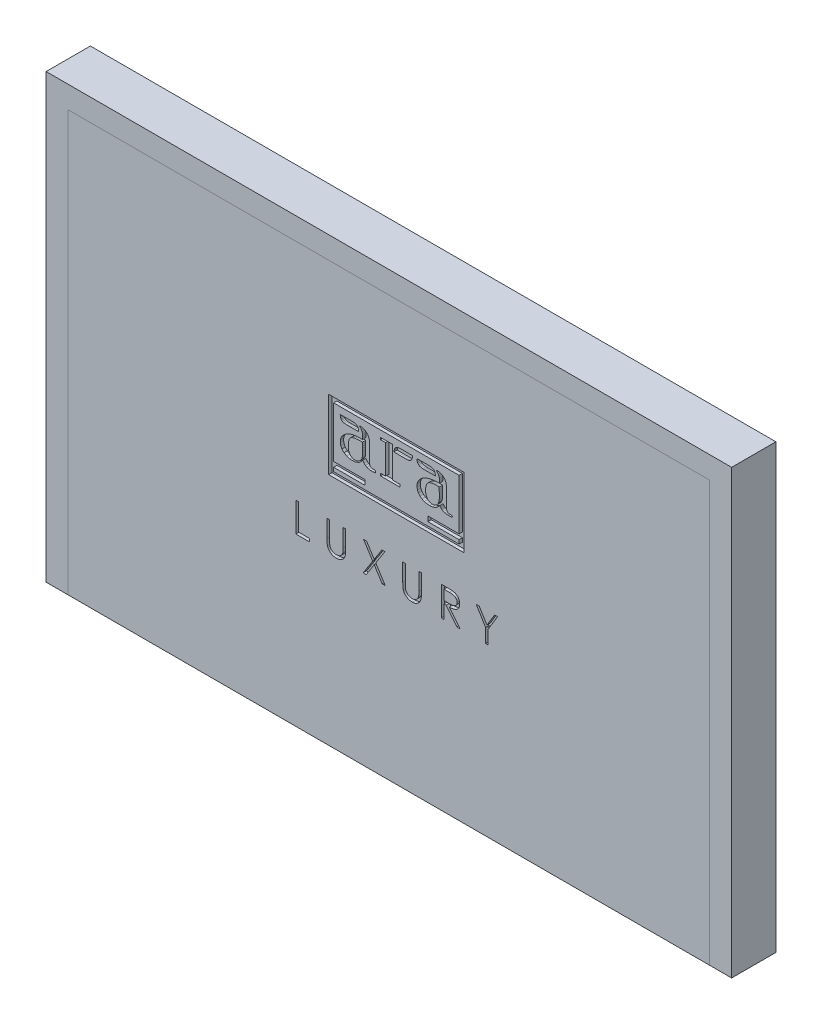
SolidWorks part; units mm, degrees
ref_plane "Front Plane" through (0, 0, 0) normal (0, 0, 1) x (1, 0, 0)
ref_plane "Top Plane" through (0, 0, 0) normal (0, 1, 0) x (1, 0, 0)
ref_plane "Right Plane" through (0, 0, 0) normal (1, 0, 0) x (0, 0, -1)
sketch "Sketch1" plane through (0, 0, 0) normal (0, 0, 1) x (1, 0, 0)
  line L0 (290, -200) -> (310, -200)
  line L1 (-310, 200) -> (310, 200)
  line L2 (-310, 200) -> (-310, -200)
  line L3 (-310, -200) -> (290, -200)
  line L4 (310, 200) -> (310, -200)
  line L5 (-310, -200) -> (-290, -200)
  line L6 (-310, -200) -> (-310, 200)
  line L7 (-310, 200) -> (-290, 200)
  line L8 (-290, -200) -> (-290, 180)
  line L9 (-310, 200) -> (310, 200)
  line L10 (-310, 200) -> (-310, 180)
  line L11 (-290, 180) -> (290, 180)
  line L12 (310, 200) -> (310, 180)
  line L13 (310, 200) -> (290, 200)
  line L14 (310, 200) -> (310, -200)
  line L15 (310, -200) -> (290, -200)
  line L16 (290, 180) -> (290, -200)
  point P0 (0, 0)
  point P7 (0, 200)
  point P8 (-310, 0)
  dimension "D1" = 620
  dimension "D2" = 400
  dimension "D3" = 20
  dimension "D4" = 20
  dimension "D5" = 20
extrude "Boss-Extrude3" add sketch "Sketch1" along normal blind 40 contours L16 L11 L8 L3 region at (0, -10, 0)
extrude "Boss-Extrude4" add sketch "Sketch1<6>" along normal blind 40 separate body contours L11 L16 L0 L4 L9 L1 L2 L6 L3 L8 region at (297.3783, -10, 0)
sketch "Sketch1<6>" plane through (0, 0, 0) normal (0, 0, 1) x (1, 0, 0) same geometry as "Sketch1"
sketch "Sketch8" plane through (0, 0, 40) normal (0, 0, 1) x (1, 0, 0)
  line L0 (-349.1542, 130) -> (342.1107, 130) construction
  line L1 (-310, 200) -> (310, 200) construction
  text T0 "LUXURY" font "Century Gothic" height in points 100
  dimension "D1" = 70
extrude "Cut-Extrude1" cut sketch "Sketch8" against normal blind 3
sketch "Sketch9" plane through (0, 0, 40) normal (0, 0, 1) x (1, 0, 0)
  line L0 (-340.0983, 130) -> (368.2721, 130) construction
  line L1 (-310, 200) -> (310, 200) construction
  dimension "D1" = 70
sketch "Sketch10" plane through (0, 0, 40) normal (0, 0, 1) x (1, 0, 0)
  line L24 (-49.9679, 20.0654) -> (-49.9679, 16.5579)
  line L25 (-21.4314, 20.0654) -> (-49.9679, 20.0654)
  line L26 (-21.4314, 24.5654) -> (-21.4314, 20.0654)
  line L27 (-49.9679, 24.5654) -> (-21.4314, 24.5654)
  line L28 (-49.9679, 70.5) -> (-49.9679, 24.5654)
  line L29 (63.4321, 70.5) -> (-49.9679, 70.5)
  line L30 (63.4321, 24.5654) -> (63.4321, 70.5)
  line L31 (35.2971, 24.5654) -> (63.4321, 24.5654)
  line L32 (35.2971, 20.0654) -> (35.2971, 24.5654)
  line L33 (63.4321, 20.0654) -> (35.2971, 20.0654)
  line L34 (63.4321, 16.5579) -> (63.4321, 20.0654)
  line L35 (-49.9679, 16.5579) -> (63.4321, 16.5579)
  line L76 (-14.5603, 25.6878) -> (-14.4285, 25.6889)
  line L77 (-14.9757, 25.6878) -> (-14.5603, 25.6878)
  line L78 (-14.9757, 27.085) -> (-14.9757, 25.6878)
  line L79 (-14.6075, 27.085) -> (-14.9757, 27.085)
  line L80 (-14.4416, 27.0821) -> (-14.6075, 27.085)
  line L81 (-14.2917, 27.0737) -> (-14.4416, 27.0821)
  line L82 (-14.1577, 27.0597) -> (-14.2917, 27.0737)
  line L83 (-14.0393, 27.0405) -> (-14.1577, 27.0597)
  line L84 (-13.9365, 27.0162) -> (-14.0393, 27.0405)
  line L85 (-13.849, 26.9869) -> (-13.9365, 27.0162)
  line L86 (-13.7767, 26.9529) -> (-13.849, 26.9869)
  line L87 (-13.6976, 26.8962) -> (-13.7767, 26.9529)
  line L88 (-13.6301, 26.8312) -> (-13.6976, 26.8962)
  line L89 (-13.5746, 26.7579) -> (-13.6301, 26.8312)
  line L90 (-13.5311, 26.676) -> (-13.5746, 26.7579)
  line L91 (-13.4998, 26.5853) -> (-13.5311, 26.676)
  line L92 (-13.481, 26.4857) -> (-13.4998, 26.5853)
  line L93 (-13.4746, 26.377) -> (-13.481, 26.4857)
  line L94 (-13.4769, 26.3134) -> (-13.4746, 26.377)
  line L95 (-13.4839, 26.2523) -> (-13.4769, 26.3134)
  line L96 (-13.4954, 26.1939) -> (-13.4839, 26.2523)
  line L97 (-13.5116, 26.1382) -> (-13.4954, 26.1939)
  line L98 (-13.5324, 26.0856) -> (-13.5116, 26.1382)
  line L99 (-13.5578, 26.0361) -> (-13.5324, 26.0856)
  line L100 (-13.5879, 25.9899) -> (-13.5578, 26.0361)
  line L101 (-13.6185, 25.9436) -> (-13.5879, 25.9899)
  line L102 (-13.6533, 25.9018) -> (-13.6185, 25.9436)
  line L103 (-13.6922, 25.8643) -> (-13.6533, 25.9018)
  line L104 (-13.7346, 25.8309) -> (-13.6922, 25.8643)
  line L105 (-13.7804, 25.8014) -> (-13.7346, 25.8309)
  line L106 (-13.8292, 25.7758) -> (-13.7804, 25.8014)
  line L107 (-13.8806, 25.7538) -> (-13.8292, 25.7758)
  line L108 (-13.943, 25.7353) -> (-13.8806, 25.7538)
  line L109 (-14.017, 25.7201) -> (-13.943, 25.7353)
  line L110 (-14.1025, 25.708) -> (-14.017, 25.7201)
  line L111 (-14.1996, 25.6989) -> (-14.1025, 25.708)
  line L112 (-14.3083, 25.6926) -> (-14.1996, 25.6989)
  line L113 (-14.4285, 25.6889) -> (-14.3083, 25.6926)
  line L184 (-36.331, 47.0631) -> (-36.431, 46.0338)
  line L185 (-36.2105, 48.0868) -> (-36.331, 47.0631)
  line L186 (-36.0553, 48.7996) -> (-36.2105, 48.0868)
  line L187 (-35.7856, 49.4505) -> (-36.0553, 48.7996)
  line L188 (-35.4123, 50.0372) -> (-35.7856, 49.4505)
  line L189 (-34.9466, 50.5572) -> (-35.4123, 50.0372)
  line L190 (-34.3994, 51.0079) -> (-34.9466, 50.5572)
  line L191 (-33.7817, 51.3869) -> (-34.3994, 51.0079)
  line L192 (-33.1046, 51.6918) -> (-33.7817, 51.3869)
  line L193 (-31.8319, 52.108) -> (-33.1046, 51.6918)
  line L194 (-30.5454, 52.4072) -> (-31.8319, 52.108)
  line L195 (-29.2481, 52.6051) -> (-30.5454, 52.4072)
  line L196 (-27.9427, 52.7178) -> (-29.2481, 52.6051)
  line L197 (-26.6321, 52.7611) -> (-27.9427, 52.7178)
  line L198 (-25.3192, 52.751) -> (-26.6321, 52.7611)
  line L199 (-24.0068, 52.7033) -> (-25.3192, 52.751)
  line L200 (-24.0016, 51.0225) -> (-24.0068, 52.7033)
  line L201 (-23.9899, 49.3656) -> (-24.0016, 51.0225)
  line L202 (-23.9775, 47.7287) -> (-23.9899, 49.3656)
  line L203 (-23.9703, 46.108) -> (-23.9775, 47.7287)
  line L204 (-23.9741, 44.4999) -> (-23.9703, 46.108)
  line L205 (-23.9947, 42.9003) -> (-23.9741, 44.4999)
  line L206 (-24.0381, 41.3057) -> (-23.9947, 42.9003)
  line L207 (-24.2689, 40.0096) -> (-24.0381, 41.3057)
  line L208 (-24.8291, 38.7828) -> (-24.2689, 40.0096)
  line L209 (-25.6608, 37.6717) -> (-24.8291, 38.7828)
  line L210 (-26.7064, 36.7225) -> (-25.6608, 37.6717)
  line L211 (-27.908, 35.9817) -> (-26.7064, 36.7225)
  line L212 (-29.2079, 35.4954) -> (-27.908, 35.9817)
  line L213 (-30.5482, 35.31) -> (-29.2079, 35.4954)
  line L214 (-31.8358, 35.4287) -> (-30.5482, 35.31)
  line L215 (-33.0328, 35.8086) -> (-31.8358, 35.4287)
  line L216 (-34.1061, 36.4284) -> (-33.0328, 35.8086)
  line L217 (-35.0224, 37.2666) -> (-34.1061, 36.4284)
  line L218 (-35.7487, 38.3016) -> (-35.0224, 37.2666)
  line L219 (-36.2518, 39.5122) -> (-35.7487, 38.3016)
  line L220 (-36.4984, 40.8767) -> (-36.2518, 39.5122)
  line L221 (-36.5546, 41.9025) -> (-36.4984, 40.8767)
  line L222 (-36.5724, 42.9332) -> (-36.5546, 41.9025)
  line L223 (-36.5553, 43.9667) -> (-36.5724, 42.9332)
  line L224 (-36.507, 45.0009) -> (-36.5553, 43.9667)
  line L225 (-36.431, 46.0338) -> (-36.507, 45.0009)
  line L268 (35.6902, 50.7229) -> (35.3135, 50.4294)
  line L269 (36.092, 50.9831) -> (35.6902, 50.7229)
  line L270 (36.5053, 51.2052) -> (36.092, 50.9831)
  line L271 (36.9164, 51.3843) -> (36.5053, 51.2052)
  line L272 (38.1178, 51.7846) -> (36.9164, 51.3843)
  line L273 (39.3336, 52.0756) -> (38.1178, 51.7846)
  line L274 (40.5593, 52.2699) -> (39.3336, 52.0756)
  line L275 (41.79, 52.3798) -> (40.5593, 52.2699)
  line L276 (43.021, 52.4178) -> (41.79, 52.3798)
  line L277 (44.2478, 52.3964) -> (43.021, 52.4178)
  line L278 (45.4654, 52.328) -> (44.2478, 52.3964)
  line L279 (45.4886, 50.7056) -> (45.4654, 52.328)
  line L280 (45.5412, 49.0885) -> (45.4886, 50.7056)
  line L281 (45.5977, 47.479) -> (45.5412, 49.0885)
  line L282 (45.6329, 45.8793) -> (45.5977, 47.479)
  line L283 (45.6213, 44.2918) -> (45.6329, 45.8793)
  line L284 (45.5376, 42.7186) -> (45.6213, 44.2918)
  line L285 (45.3564, 41.1622) -> (45.5376, 42.7186)
  line L286 (44.7591, 39.2392) -> (45.3564, 41.1622)
  line L287 (43.6933, 37.6897) -> (44.7591, 39.2392)
  line L288 (42.2799, 36.554) -> (43.6933, 37.6897)
  line L289 (40.6393, 35.8726) -> (42.2799, 36.554)
  line L290 (38.8922, 35.6856) -> (40.6393, 35.8726)
  line L291 (37.1593, 36.0334) -> (38.8922, 35.6856)
  line L292 (35.5611, 36.9565) -> (37.1593, 36.0334)
  line L293 (35.3751, 37.1123) -> (35.5611, 36.9565)
  line L294 (35.1901, 37.2758) -> (35.3751, 37.1123)
  line L295 (35.0106, 37.4472) -> (35.1901, 37.2758)
  line L296 (34.8411, 37.6268) -> (35.0106, 37.4472)
  line L297 (34.6863, 37.8148) -> (34.8411, 37.6268)
  line L298 (34.5506, 38.0113) -> (34.6863, 37.8148)
  line L299 (34.4384, 38.2167) -> (34.5506, 38.0113)
  line L300 (33.794, 39.8153) -> (34.4384, 38.2167)
  line L301 (33.3635, 41.4187) -> (33.794, 39.8153)
  line L302 (33.1485, 43.024) -> (33.3635, 41.4187)
  line L303 (33.1503, 44.6277) -> (33.1485, 43.024)
  line L304 (33.3703, 46.2269) -> (33.1503, 44.6277)
  line L305 (33.8099, 47.8183) -> (33.3703, 46.2269)
  line L306 (34.4705, 49.3987) -> (33.8099, 47.8183)
  line L307 (34.69, 49.7624) -> (34.4705, 49.3987)
  line L308 (34.9756, 50.1076) -> (34.69, 49.7624)
  line L309 (35.3135, 50.4294) -> (34.9756, 50.1076)
  line L344 (-1.446, 25.6878) -> (-1.2755, 25.6912)
  line L345 (-1.8519, 25.6878) -> (-1.446, 25.6878)
  line L346 (-1.8519, 27.085) -> (-1.8519, 25.6878)
  line L347 (-1.4932, 27.085) -> (-1.8519, 27.085)
  line L348 (-1.3504, 27.0833) -> (-1.4932, 27.085)
  line L349 (-1.2213, 27.0783) -> (-1.3504, 27.0833)
  line L350 (-1.1058, 27.0701) -> (-1.2213, 27.0783)
  line L351 (-1.0036, 27.059) -> (-1.1058, 27.0701)
  line L352 (-0.9146, 27.0451) -> (-1.0036, 27.059)
  line L353 (-0.8387, 27.0285) -> (-0.9146, 27.0451)
  line L354 (-0.7757, 27.0095) -> (-0.8387, 27.0285)
  line L355 (-0.7242, 26.9875) -> (-0.7757, 27.0095)
  line L356 (-0.6751, 26.9619) -> (-0.7242, 26.9875)
  line L357 (-0.6283, 26.9325) -> (-0.6751, 26.9619)
  line L358 (-0.5837, 26.8991) -> (-0.6283, 26.9325)
  line L359 (-0.5416, 26.8616) -> (-0.5837, 26.8991)
  line L360 (-0.5017, 26.8198) -> (-0.5416, 26.8616)
  line L361 (-0.4641, 26.7735) -> (-0.5017, 26.8198)
  line L362 (-0.434, 26.7273) -> (-0.4641, 26.7735)
  line L363 (-0.4086, 26.6778) -> (-0.434, 26.7273)
  line L364 (-0.3878, 26.6251) -> (-0.4086, 26.6778)
  line L365 (-0.3716, 26.5695) -> (-0.3878, 26.6251)
  line L366 (-0.36, 26.511) -> (-0.3716, 26.5695)
  line L367 (-0.3531, 26.45) -> (-0.36, 26.511)
  line L368 (-0.3508, 26.3864) -> (-0.3531, 26.45)
  line L369 (-0.3554, 26.2852) -> (-0.3508, 26.3864)
  line L370 (-0.3695, 26.1922) -> (-0.3554, 26.2852)
  line L371 (-0.3932, 26.1072) -> (-0.3695, 26.1922)
  line L372 (-0.4266, 26.0303) -> (-0.3932, 26.1072)
  line L373 (-0.4699, 25.9615) -> (-0.4266, 26.0303)
  line L374 (-0.5232, 25.9008) -> (-0.4699, 25.9615)
  line L375 (-0.5869, 25.8482) -> (-0.5232, 25.9008)
  line L376 (-0.6602, 25.8066) -> (-0.5869, 25.8482)
  line L377 (-0.7506, 25.771) -> (-0.6602, 25.8066)
  line L378 (-0.8576, 25.7415) -> (-0.7506, 25.771)
  line L379 (-0.981, 25.7182) -> (-0.8576, 25.7415)
  line L380 (-1.1204, 25.7014) -> (-0.981, 25.7182)
  line L381 (-1.2755, 25.6912) -> (-1.1204, 25.7014)
  line L851 (28.2851, 24.6115) -> (30.702, 24.6115)
  line L852 (30.702, 24.6115) -> (30.702, 25.8577)
  line L853 (30.702, 25.8577) -> (28.2851, 25.8577)
  line L854 (28.2851, 25.8577) -> (28.2851, 27.0756)
  line L855 (28.2851, 27.0756) -> (30.702, 27.0756)
  line L856 (30.702, 27.0756) -> (30.702, 28.3407)
  line L857 (30.702, 28.3407) -> (27.0011, 28.3407)
  line L858 (27.0011, 28.3407) -> (27.0011, 21.562)
  line L859 (27.0011, 21.562) -> (30.702, 21.562)
  line L860 (30.702, 21.562) -> (30.702, 22.827)
  line L861 (30.702, 22.827) -> (28.2851, 22.827)
  line L862 (28.2851, 22.827) -> (28.2851, 24.6115)
  line L863 (24.5286, 21.562) -> (23.3957, 28.3407)
  line L864 (23.3957, 28.3407) -> (22.14, 28.3407)
  line L865 (22.14, 28.3407) -> (20.5633, 23.6107)
  line L866 (20.5633, 23.6107) -> (18.9772, 28.3407)
  line L867 (18.9772, 28.3407) -> (17.731, 28.3407)
  line L868 (17.731, 28.3407) -> (16.5603, 21.562)
  line L869 (16.5603, 21.562) -> (17.8159, 21.562)
  line L870 (17.8159, 21.562) -> (18.5618, 25.8388)
  line L871 (18.5618, 25.8388) -> (19.9874, 21.562)
  line L872 (19.9874, 21.562) -> (21.1204, 21.562)
  line L873 (21.1204, 21.562) -> (22.5648, 25.8388)
  line L874 (22.5648, 25.8388) -> (23.2824, 21.562)
  line L875 (23.2824, 21.562) -> (24.5286, 21.562)
  line L876 (10.8683, 23.8046) -> (10.866, 23.9601)
  line L877 (10.866, 23.9601) -> (10.866, 28.3407)
  line L878 (10.866, 28.3407) -> (9.5725, 28.3407)
  line L879 (9.5725, 28.3407) -> (9.5725, 24.3)
  line L880 (9.5725, 24.3) -> (9.5772, 23.967)
  line L881 (9.5772, 23.967) -> (9.5913, 23.6637)
  line L882 (9.5913, 23.6637) -> (9.6149, 23.3898)
  line L883 (9.6149, 23.3898) -> (9.6483, 23.145)
  line L884 (9.6483, 23.145) -> (9.6916, 22.9289)
  line L885 (9.6916, 22.9289) -> (9.7449, 22.7412)
  line L886 (9.7449, 22.7412) -> (9.8085, 22.5816)
  line L887 (9.8085, 22.5816) -> (9.8802, 22.4394)
  line L888 (9.8802, 22.4394) -> (9.9656, 22.3042)
  line L889 (9.9656, 22.3042) -> (10.0645, 22.1758)
  line L890 (10.0645, 22.1758) -> (10.1767, 22.0545)
  line L891 (10.1767, 22.0545) -> (10.3022, 21.94)
  line L892 (10.3022, 21.94) -> (10.4408, 21.8325)
  line L893 (10.4408, 21.8325) -> (10.5922, 21.7319)
  line L894 (10.5922, 21.7319) -> (10.75, 21.6418)
  line L895 (10.75, 21.6418) -> (10.9159, 21.5655)
  line L896 (10.9159, 21.5655) -> (11.0899, 21.503)
  line L897 (11.0899, 21.503) -> (11.2719, 21.4545)
  line L898 (11.2719, 21.4545) -> (11.4621, 21.4198)
  line L899 (11.4621, 21.4198) -> (11.6604, 21.399)
  line L900 (11.6604, 21.399) -> (11.8667, 21.392)
  line L901 (11.8667, 21.392) -> (12.0257, 21.3955)
  line L902 (12.0257, 21.3955) -> (12.1789, 21.4061)
  line L903 (12.1789, 21.4061) -> (12.3263, 21.424)
  line L904 (12.3263, 21.424) -> (12.4679, 21.4493)
  line L905 (12.4679, 21.4493) -> (12.6037, 21.4822)
  line L906 (12.6037, 21.4822) -> (12.7338, 21.5228)
  line L907 (12.7338, 21.5228) -> (12.858, 21.5714)
  line L908 (12.858, 21.5714) -> (12.9771, 21.6245)
  line L909 (12.9771, 21.6245) -> (13.0918, 21.6866)
  line L910 (13.0918, 21.6866) -> (13.2021, 21.7572)
  line L911 (13.2021, 21.7572) -> (13.3083, 21.8361)
  line L912 (13.3083, 21.8361) -> (13.4106, 21.9229)
  line L913 (13.4106, 21.9229) -> (13.509, 22.0173)
  line L914 (13.509, 22.0173) -> (13.6038, 22.119)
  line L915 (13.6038, 22.119) -> (13.6928, 22.2248)
  line L916 (13.6928, 22.2248) -> (13.7736, 22.3317)
  line L917 (13.7736, 22.3317) -> (13.8459, 22.4398)
  line L918 (13.8459, 22.4398) -> (13.9096, 22.5491)
  line L919 (13.9096, 22.5491) -> (13.9646, 22.6595)
  line L920 (13.9646, 22.6595) -> (14.0107, 22.771)
  line L921 (14.0107, 22.771) -> (14.0476, 22.8838)
  line L922 (14.0476, 22.8838) -> (14.0777, 23.0098)
  line L923 (14.0777, 23.0098) -> (14.1031, 23.1612)
  line L924 (14.1031, 23.1612) -> (14.1239, 23.3381)
  line L925 (14.1239, 23.3381) -> (14.1401, 23.5404)
  line L926 (14.1401, 23.5404) -> (14.1516, 23.7682)
  line L927 (14.1516, 23.7682) -> (14.1586, 24.0213)
  line L928 (14.1586, 24.0213) -> (14.1609, 24.3)
  line L929 (14.1609, 24.3) -> (14.1609, 28.3407)
  line L930 (14.1609, 28.3407) -> (12.8674, 28.3407)
  line L931 (12.8674, 28.3407) -> (12.8674, 24.1205)
  line L932 (12.8674, 24.1205) -> (12.8657, 23.932)
  line L933 (12.8657, 23.932) -> (12.8603, 23.7629)
  line L934 (12.8603, 23.7629) -> (12.8511, 23.6127)
  line L935 (12.8511, 23.6127) -> (12.838, 23.4812)
  line L936 (12.838, 23.4812) -> (12.8207, 23.368)
  line L937 (12.8207, 23.368) -> (12.7991, 23.2728)
  line L938 (12.7991, 23.2728) -> (12.773, 23.1953)
  line L939 (12.773, 23.1953) -> (12.7418, 23.1283)
  line L940 (12.7418, 23.1283) -> (12.7049, 23.0647)
  line L941 (12.7049, 23.0647) -> (12.6621, 23.0045)
  line L942 (12.6621, 23.0045) -> (12.6135, 22.9479)
  line L943 (12.6135, 22.9479) -> (12.5592, 22.8947)
  line L944 (12.5592, 22.8947) -> (12.4991, 22.845)
  line L945 (12.4991, 22.845) -> (12.4332, 22.7988)
  line L946 (12.4332, 22.7988) -> (12.3591, 22.7572)
  line L947 (12.3591, 22.7572) -> (12.2824, 22.7215)
  line L948 (12.2824, 22.7215) -> (12.2028, 22.692)
  line L949 (12.2028, 22.692) -> (12.1198, 22.6687)
  line L950 (12.1198, 22.6687) -> (12.0333, 22.6519)
  line L951 (12.0333, 22.6519) -> (11.9427, 22.6417)
  line L952 (11.9427, 22.6417) -> (11.8479, 22.6383)
  line L953 (11.8479, 22.6383) -> (11.7566, 22.6411)
  line L954 (11.7566, 22.6411) -> (11.6689, 22.6498)
  line L955 (11.6689, 22.6498) -> (11.585, 22.6643)
  line L956 (11.585, 22.6643) -> (11.5051, 22.6845)
  line L957 (11.5051, 22.6845) -> (11.4293, 22.7105)
  line L958 (11.4293, 22.7105) -> (11.3578, 22.7423)
  line L959 (11.3578, 22.7423) -> (11.2908, 22.7798)
  line L960 (11.2908, 22.7798) -> (11.2289, 22.8221)
  line L961 (11.2289, 22.8221) -> (11.1727, 22.8679)
  line L962 (11.1727, 22.8679) -> (11.1219, 22.9176)
  line L963 (11.1219, 22.9176) -> (11.0763, 22.9712)
  line L964 (11.0763, 22.9712) -> (11.0359, 23.029)
  line L965 (11.0359, 23.029) -> (11.0005, 23.091)
  line L966 (11.0005, 23.091) -> (10.9698, 23.1575)
  line L967 (10.9698, 23.1575) -> (10.9432, 23.2297)
  line L968 (10.9432, 23.2297) -> (10.9203, 23.3166)
  line L969 (10.9203, 23.3166) -> (10.9012, 23.4179)
  line L970 (10.9012, 23.4179) -> (10.886, 23.5332)
  line L971 (10.886, 23.5332) -> (10.875, 23.6622)
  line L972 (10.875, 23.6622) -> (10.8683, 23.8046)
  line L973 (4.9749, 27.0944) -> (7.0519, 27.0944)
  line L974 (7.0519, 27.0944) -> (7.0519, 28.3407)
  line L975 (7.0519, 28.3407) -> (3.6908, 28.3407)
  line L976 (3.6908, 28.3407) -> (3.6908, 21.562)
  line L977 (3.6908, 21.562) -> (4.9749, 21.562)
  line L978 (4.9749, 21.562) -> (4.9749, 24.6115)
  line L979 (4.9749, 24.6115) -> (7.0519, 24.6115)
  line L980 (7.0519, 24.6115) -> (7.0519, 25.8577)
  line L981 (7.0519, 25.8577) -> (4.9749, 25.8577)
  line L982 (4.9749, 25.8577) -> (4.9749, 27.0944)
  line L983 (-1.7198, 24.4321) -> (-0.1998, 21.562)
  line L984 (-0.1998, 21.562) -> (1.2164, 21.562)
  line L985 (1.2164, 21.562) -> (-0.3886, 24.5737)
  line L986 (-0.3886, 24.5737) -> (-0.2094, 24.6431)
  line L987 (-0.2094, 24.6431) -> (-0.0441, 24.7217)
  line L988 (-0.0441, 24.7217) -> (0.1074, 24.8095)
  line L989 (0.1074, 24.8095) -> (0.2449, 24.9066)
  line L990 (0.2449, 24.9066) -> (0.3686, 25.013)
  line L991 (0.3686, 25.013) -> (0.4784, 25.1286)
  line L992 (0.4784, 25.1286) -> (0.5744, 25.2535)
  line L993 (0.5744, 25.2535) -> (0.6606, 25.3871)
  line L994 (0.6606, 25.3871) -> (0.733, 25.5291)
  line L995 (0.733, 25.5291) -> (0.7919, 25.6798)
  line L996 (0.7919, 25.6798) -> (0.8374, 25.8396)
  line L997 (0.8374, 25.8396) -> (0.8697, 26.0089)
  line L998 (0.8697, 26.0089) -> (0.889, 26.1879)
  line L999 (0.889, 26.1879) -> (0.8954, 26.377)
  line L1000 (0.8954, 26.377) -> (0.8896, 26.5521)
  line L1001 (0.8896, 26.5521) -> (0.872, 26.7212)
  line L1002 (0.872, 26.7212) -> (0.8426, 26.8843)
  line L1003 (0.8426, 26.8843) -> (0.8011, 27.0411)
  line L1004 (0.8011, 27.0411) -> (0.7474, 27.1914)
  line L1005 (0.7474, 27.1914) -> (0.6814, 27.3352)
  line L1006 (0.6814, 27.3352) -> (0.6028, 27.4721)
  line L1007 (0.6028, 27.4721) -> (0.5178, 27.6004)
  line L1008 (0.5178, 27.6004) -> (0.4247, 27.7181)
  line L1009 (0.4247, 27.7181) -> (0.3235, 27.8251)
  line L1010 (0.3235, 27.8251) -> (0.2143, 27.9212)
  line L1011 (0.2143, 27.9212) -> (0.0969, 28.0063)
  line L1012 (0.0969, 28.0063) -> (-0.0285, 28.0801)
  line L1013 (-0.0285, 28.0801) -> (-0.162, 28.1425)
  line L1014 (-0.162, 28.1425) -> (-0.3124, 28.1951)
  line L1015 (-0.3124, 28.1951) -> (-0.4885, 28.2396)
  line L1016 (-0.4885, 28.2396) -> (-0.6907, 28.276)
  line L1017 (-0.6907, 28.276) -> (-0.9193, 28.3043)
  line L1018 (-0.9193, 28.3043) -> (-1.1747, 28.3245)
  line L1019 (-1.1747, 28.3245) -> (-1.4571, 28.3366)
  line L1020 (-1.4571, 28.3366) -> (-1.767, 28.3407)
  line L1021 (-1.767, 28.3407) -> (-3.136, 28.3407)
  line L1022 (-3.136, 28.3407) -> (-3.136, 21.562)
  line L1023 (-3.136, 21.562) -> (-1.8519, 21.562)
  line L1024 (-1.8519, 21.562) -> (-1.8519, 24.4321)
  line L1025 (-1.8519, 24.4321) -> (-1.7198, 24.4321)
  line L1026 (-9.5371, 21.562) -> (-5.8361, 21.562)
  line L1027 (-5.8361, 21.562) -> (-5.8361, 22.827)
  line L1028 (-5.8361, 22.827) -> (-8.2531, 22.827)
  line L1029 (-8.2531, 22.827) -> (-8.2531, 24.6115)
  line L1030 (-8.2531, 24.6115) -> (-5.8361, 24.6115)
  line L1031 (-5.8361, 24.6115) -> (-5.8361, 25.8577)
  line L1032 (-5.8361, 25.8577) -> (-8.2531, 25.8577)
  line L1033 (-8.2531, 25.8577) -> (-8.2531, 27.0756)
  line L1034 (-8.2531, 27.0756) -> (-5.8361, 27.0756)
  line L1035 (-5.8361, 27.0756) -> (-5.8361, 28.3407)
  line L1036 (-5.8361, 28.3407) -> (-9.5371, 28.3407)
  line L1037 (-9.5371, 28.3407) -> (-9.5371, 21.562)
  line L1038 (-14.5843, 28.3366) -> (-14.8907, 28.3407)
  line L1039 (-14.8907, 28.3407) -> (-16.2597, 28.3407)
  line L1040 (-16.2597, 28.3407) -> (-16.2597, 21.562)
  line L1041 (-16.2597, 21.562) -> (-14.9757, 21.562)
  line L1042 (-14.9757, 21.562) -> (-14.9757, 24.4321)
  line L1043 (-14.9757, 24.4321) -> (-14.7052, 24.4344)
  line L1044 (-14.7052, 24.4344) -> (-14.4599, 24.4411)
  line L1045 (-14.4599, 24.4411) -> (-14.2397, 24.4522)
  line L1046 (-14.2397, 24.4522) -> (-14.0445, 24.4673)
  line L1047 (-14.0445, 24.4673) -> (-13.8741, 24.4864)
  line L1048 (-13.8741, 24.4864) -> (-13.7282, 24.5094)
  line L1049 (-13.7282, 24.5094) -> (-13.6068, 24.5359)
  line L1050 (-13.6068, 24.5359) -> (-13.4304, 24.5943)
  line L1051 (-13.4304, 24.5943) -> (-13.2653, 24.6645)
  line L1052 (-13.2653, 24.6645) -> (-13.1111, 24.7465)
  line L1053 (-13.1111, 24.7465) -> (-12.9674, 24.8406)
  line L1054 (-12.9674, 24.8406) -> (-12.834, 24.9469)
  line L1055 (-12.834, 24.9469) -> (-12.7105, 25.0656)
  line L1056 (-12.7105, 25.0656) -> (-12.5965, 25.1968)
  line L1057 (-12.5965, 25.1968) -> (-12.4989, 25.335)
  line L1058 (-12.4989, 25.335) -> (-12.4162, 25.4828)
  line L1059 (-12.4162, 25.4828) -> (-12.3486, 25.6405)
  line L1060 (-12.3486, 25.6405) -> (-12.296, 25.8085)
  line L1061 (-12.296, 25.8085) -> (-12.2584, 25.987)
  line L1062 (-12.2584, 25.987) -> (-12.2359, 26.1763)
  line L1063 (-12.2359, 26.1763) -> (-12.2284, 26.377)
  line L1064 (-12.2284, 26.377) -> (-12.2342, 26.5556)
  line L1065 (-12.2342, 26.5556) -> (-12.2515, 26.727)
  line L1066 (-12.2515, 26.727) -> (-12.2804, 26.8912)
  line L1067 (-12.2804, 26.8912) -> (-12.3209, 27.048)
  line L1068 (-12.3209, 27.048) -> (-12.3729, 27.1972)
  line L1069 (-12.3729, 27.1972) -> (-12.4364, 27.3386)
  line L1070 (-12.4364, 27.3386) -> (-12.5116, 27.4721)
  line L1071 (-12.5116, 27.4721) -> (-12.5966, 27.5969)
  line L1072 (-12.5966, 27.5969) -> (-12.6899, 27.7121)
  line L1073 (-12.6899, 27.7121) -> (-12.7915, 27.8174)
  line L1074 (-12.7915, 27.8174) -> (-12.9018, 27.9125)
  line L1075 (-12.9018, 27.9125) -> (-13.0208, 27.997)
  line L1076 (-13.0208, 27.997) -> (-13.1487, 28.0706)
  line L1077 (-13.1487, 28.0706) -> (-13.2857, 28.133)
  line L1078 (-13.2857, 28.133) -> (-13.4396, 28.1891)
  line L1079 (-13.4396, 28.1891) -> (-13.618, 28.2361)
  line L1080 (-13.618, 28.2361) -> (-13.8213, 28.2742)
  line L1081 (-13.8213, 28.2742) -> (-14.05, 28.3035)
  line L1082 (-14.05, 28.3035) -> (-14.3042, 28.3243)
  line L1083 (-14.3042, 28.3243) -> (-14.5843, 28.3366)
  line L1084 (30.0246, 35.1575) -> (32.0574, 34.2463)
  line L1085 (32.0574, 34.2463) -> (34.3493, 33.63)
  line L1086 (34.3493, 33.63) -> (36.7974, 33.3967)
  line L1087 (36.7974, 33.3967) -> (39.2986, 33.6344)
  line L1088 (39.2986, 33.6344) -> (41.7497, 34.4312)
  line L1089 (41.7497, 34.4312) -> (44.0476, 35.8751)
  line L1090 (44.0476, 35.8751) -> (46.0892, 38.054)
  line L1091 (46.0892, 38.054) -> (46.4015, 37.6887)
  line L1092 (46.4015, 37.6887) -> (46.6989, 37.3226)
  line L1093 (46.6989, 37.3226) -> (46.9887, 36.9622)
  line L1094 (46.9887, 36.9622) -> (47.278, 36.6141)
  line L1095 (47.278, 36.6141) -> (47.5741, 36.2848)
  line L1096 (47.5741, 36.2848) -> (47.8842, 35.981)
  line L1097 (47.8842, 35.981) -> (48.2156, 35.7093)
  line L1098 (48.2156, 35.7093) -> (49.3955, 35.0153)
  line L1099 (49.3955, 35.0153) -> (50.6215, 34.5922)
  line L1100 (50.6215, 34.5922) -> (51.883, 34.3794)
  line L1101 (51.883, 34.3794) -> (53.1694, 34.3163)
  line L1102 (53.1694, 34.3163) -> (54.47, 34.3422)
  line L1103 (54.47, 34.3422) -> (55.7744, 34.3965)
  line L1104 (55.7744, 34.3965) -> (57.0718, 34.4186)
  line L1105 (57.0718, 34.4186) -> (57.1431, 34.4445)
  line L1106 (57.1431, 34.4445) -> (57.2248, 34.515)
  line L1107 (57.2248, 34.515) -> (57.3083, 34.6171)
  line L1108 (57.3083, 34.6171) -> (57.3847, 34.7377)
  line L1109 (57.3847, 34.7377) -> (57.4453, 34.8638)
  line L1110 (57.4453, 34.8638) -> (57.4813, 34.9824)
  line L1111 (57.4813, 34.9824) -> (57.484, 35.0805)
  line L1112 (57.484, 35.0805) -> (57.4482, 35.1997)
  line L1113 (57.4482, 35.1997) -> (57.39, 35.3222)
  line L1114 (57.39, 35.3222) -> (57.3135, 35.4422)
  line L1115 (57.3135, 35.4422) -> (57.2229, 35.5535)
  line L1116 (57.2229, 35.5535) -> (57.1221, 35.6504)
  line L1117 (57.1221, 35.6504) -> (57.0153, 35.7269)
  line L1118 (57.0153, 35.7269) -> (56.9066, 35.777)
  line L1119 (56.9066, 35.777) -> (56.7416, 35.8177)
  line L1120 (56.7416, 35.8177) -> (56.5703, 35.8387)
  line L1121 (56.5703, 35.8387) -> (56.3943, 35.8451)
  line L1122 (56.3943, 35.8451) -> (56.2152, 35.8418)
  line L1123 (56.2152, 35.8418) -> (56.0346, 35.8337)
  line L1124 (56.0346, 35.8337) -> (55.8541, 35.8259)
  line L1125 (55.8541, 35.8259) -> (55.6755, 35.8232)
  line L1126 (55.6755, 35.8232) -> (54.6038, 35.8849)
  line L1127 (54.6038, 35.8849) -> (53.7564, 36.0637)
  line L1128 (53.7564, 36.0637) -> (53.1115, 36.3808)
  line L1129 (53.1115, 36.3808) -> (52.6473, 36.8577)
  line L1130 (52.6473, 36.8577) -> (52.342, 37.5157)
  line L1131 (52.342, 37.5157) -> (52.1736, 38.3763)
  line L1132 (52.1736, 38.3763) -> (52.1205, 39.4608)
  line L1133 (52.1205, 39.4608) -> (52.1187, 41.8984)
  line L1134 (52.1187, 41.8984) -> (52.1209, 44.3361)
  line L1135 (52.1209, 44.3361) -> (52.1223, 46.7738)
  line L1136 (52.1223, 46.7738) -> (52.1179, 49.2114)
  line L1137 (52.1179, 49.2114) -> (52.1028, 51.6488)
  line L1138 (52.1028, 51.6488) -> (52.0719, 54.0858)
  line L1139 (52.0719, 54.0858) -> (52.0202, 56.5222)
  line L1140 (52.0202, 56.5222) -> (51.7376, 58.485)
  line L1141 (51.7376, 58.485) -> (51.0288, 60.2277)
  line L1142 (51.0288, 60.2277) -> (49.9404, 61.712)
  line L1143 (49.9404, 61.712) -> (48.5193, 62.8992)
  line L1144 (48.5193, 62.8992) -> (46.812, 63.7509)
  line L1145 (46.812, 63.7509) -> (44.8655, 64.2285)
  line L1146 (44.8655, 64.2285) -> (42.7263, 64.2935)
  line L1147 (42.7263, 64.2935) -> (43.8833, 63.2375)
  line L1148 (43.8833, 63.2375) -> (44.7298, 62.0929)
  line L1149 (44.7298, 62.0929) -> (45.3047, 60.8675)
  line L1150 (45.3047, 60.8675) -> (45.647, 59.5694)
  line L1151 (45.647, 59.5694) -> (45.7956, 58.2066)
  line L1152 (45.7956, 58.2066) -> (45.7895, 56.7872)
  line L1153 (45.7895, 56.7872) -> (45.6677, 55.3191)
  line L1154 (45.6677, 55.3191) -> (44.9658, 55.2888)
  line L1155 (44.9658, 55.2888) -> (44.2691, 55.2626)
  line L1156 (44.2691, 55.2626) -> (43.577, 55.2373)
  line L1157 (43.577, 55.2373) -> (42.8889, 55.2097)
  line L1158 (42.8889, 55.2097) -> (42.2041, 55.1763)
  line L1159 (42.2041, 55.1763) -> (41.522, 55.134)
  line L1160 (41.522, 55.134) -> (40.842, 55.0793)
  line L1161 (40.842, 55.0793) -> (38.5523, 54.7986)
  line L1162 (38.5523, 54.7986) -> (36.34, 54.3553)
  line L1163 (36.34, 54.3553) -> (34.2232, 53.7125)
  line L1164 (34.2232, 53.7125) -> (32.2204, 52.8331)
  line L1165 (32.2204, 52.8331) -> (30.3497, 51.6802)
  line L1166 (30.3497, 51.6802) -> (28.6296, 50.2169)
  line L1167 (28.6296, 50.2169) -> (27.0782, 48.4062)
  line L1168 (27.0782, 48.4062) -> (25.9853, 46.4329)
  line L1169 (25.9853, 46.4329) -> (25.4336, 44.3248)
  line L1170 (25.4336, 44.3248) -> (25.4012, 42.1791)
  line L1171 (25.4012, 42.1791) -> (25.866, 40.0925)
  line L1172 (25.866, 40.0925) -> (26.8062, 38.1621)
  line L1173 (26.8062, 38.1621) -> (28.1997, 36.4848)
  line L1174 (28.1997, 36.4848) -> (30.0246, 35.1575)
  line L1175 (40.6634, 63.3372) -> (39.9178, 63.9071)
  line L1176 (39.9178, 63.9071) -> (39.0174, 64.2756)
  line L1177 (39.0174, 64.2756) -> (37.9599, 64.4357)
  line L1178 (37.9599, 64.4357) -> (36.1732, 64.5001)
  line L1179 (36.1732, 64.5001) -> (34.3834, 64.5314)
  line L1180 (34.3834, 64.5314) -> (32.5894, 64.5381)
  line L1181 (32.5894, 64.5381) -> (30.7901, 64.5286)
  line L1182 (30.7901, 64.5286) -> (28.9844, 64.5114)
  line L1183 (28.9844, 64.5114) -> (27.171, 64.4949)
  line L1184 (27.171, 64.4949) -> (25.3489, 64.4875)
  line L1185 (25.3489, 64.4875) -> (25.4539, 63.1702)
  line L1186 (25.4539, 63.1702) -> (25.7705, 62.0346)
  line L1187 (25.7705, 62.0346) -> (26.2959, 61.0851)
  line L1188 (26.2959, 61.0851) -> (27.0272, 60.326)
  line L1189 (27.0272, 60.326) -> (27.9613, 59.7617)
  line L1190 (27.9613, 59.7617) -> (29.0954, 59.3965)
  line L1191 (29.0954, 59.3965) -> (30.4266, 59.2347)
  line L1192 (30.4266, 59.2347) -> (31.4662, 59.2013)
  line L1193 (31.4662, 59.2013) -> (32.5065, 59.1836)
  line L1194 (32.5065, 59.1836) -> (33.5472, 59.1775)
  line L1195 (33.5472, 59.1775) -> (34.5882, 59.1792)
  line L1196 (34.5882, 59.1792) -> (35.6294, 59.1845)
  line L1197 (35.6294, 59.1845) -> (36.6705, 59.1895)
  line L1198 (36.6705, 59.1895) -> (37.7114, 59.1903)
  line L1199 (37.7114, 59.1903) -> (38.3437, 59.1889)
  line L1200 (38.3437, 59.1889) -> (38.9762, 59.1884)
  line L1201 (38.9762, 59.1884) -> (39.6089, 59.1883)
  line L1202 (39.6089, 59.1883) -> (40.2419, 59.1886)
  line L1203 (40.2419, 59.1886) -> (40.8752, 59.1891)
  line L1204 (40.8752, 59.1891) -> (41.5091, 59.1895)
  line L1205 (41.5091, 59.1895) -> (42.1435, 59.1897)
  line L1206 (42.1435, 59.1897) -> (41.9942, 60.4923)
  line L1207 (41.9942, 60.4923) -> (41.6992, 61.6226)
  line L1208 (41.6992, 61.6226) -> (41.2564, 62.5733)
  line L1209 (41.2564, 62.5733) -> (40.6634, 63.3372)
  line L1210 (9.8323, 64.8007) -> (8.4739, 64.6629)
  line L1211 (8.4739, 64.6629) -> (7.3263, 64.3141)
  line L1212 (7.3263, 64.3141) -> (6.384, 63.7507)
  line L1213 (6.384, 63.7507) -> (5.6417, 62.9689)
  line L1214 (5.6417, 62.9689) -> (5.094, 61.9649)
  line L1215 (5.094, 61.9649) -> (4.7357, 60.7352)
  line L1216 (4.7357, 60.7352) -> (4.5614, 59.276)
  line L1217 (4.5614, 59.276) -> (6.3614, 59.2678)
  line L1218 (6.3614, 59.2678) -> (8.1522, 59.2493)
  line L1219 (8.1522, 59.2493) -> (9.935, 59.2299)
  line L1220 (9.935, 59.2299) -> (11.7109, 59.2189)
  line L1221 (11.7109, 59.2189) -> (13.4809, 59.2259)
  line L1222 (13.4809, 59.2259) -> (15.2463, 59.26)
  line L1223 (15.2463, 59.26) -> (17.008, 59.3307)
  line L1224 (17.008, 59.3307) -> (18.154, 59.513)
  line L1225 (18.154, 59.513) -> (19.1323, 59.921)
  line L1226 (19.1323, 59.921) -> (19.9396, 60.5397)
  line L1227 (19.9396, 60.5397) -> (20.5728, 61.3541)
  line L1228 (20.5728, 61.3541) -> (21.0283, 62.3492)
  line L1229 (21.0283, 62.3492) -> (21.3031, 63.5099)
  line L1230 (21.3031, 63.5099) -> (21.3936, 64.8212)
  line L1231 (21.3936, 64.8212) -> (19.7425, 64.8247)
  line L1232 (19.7425, 64.8247) -> (18.0911, 64.8326)
  line L1233 (18.0911, 64.8326) -> (16.4393, 64.841)
  line L1234 (16.4393, 64.841) -> (14.7874, 64.8459)
  line L1235 (14.7874, 64.8459) -> (13.1355, 64.8435)
  line L1236 (13.1355, 64.8435) -> (11.4838, 64.8297)
  line L1237 (11.4838, 64.8297) -> (9.8323, 64.8007)
  line L1238 (-7.78, 62.8133) -> (-2.9952, 62.8133)
  line L1239 (-2.9952, 62.8133) -> (-2.9952, 36.5926)
  line L1240 (-2.9952, 36.5926) -> (-7.5665, 36.5926)
  line L1241 (-7.5665, 36.5926) -> (-7.5665, 34.4596)
  line L1242 (-7.5665, 34.4596) -> (10.0367, 34.4596)
  line L1243 (10.0367, 34.4596) -> (10.0367, 36.6859)
  line L1244 (10.0367, 36.6859) -> (3.4322, 36.6859)
  line L1245 (3.4322, 36.6859) -> (3.4322, 64.6494)
  line L1246 (3.4322, 64.6494) -> (-7.78, 64.6494)
  line L1247 (-7.78, 64.6494) -> (-7.78, 62.8133)
  line L1248 (-32.7794, 64.3901) -> (-34.6512, 64.4286)
  line L1249 (-34.6512, 64.4286) -> (-36.5246, 64.4377)
  line L1250 (-36.5246, 64.4377) -> (-38.3991, 64.4276)
  line L1251 (-38.3991, 64.4276) -> (-40.2741, 64.408)
  line L1252 (-40.2741, 64.408) -> (-42.149, 64.3889)
  line L1253 (-42.149, 64.3889) -> (-44.0233, 64.3804)
  line L1254 (-44.0233, 64.3804) -> (-43.9261, 63.1942)
  line L1255 (-43.9261, 63.1942) -> (-43.6646, 62.1344)
  line L1256 (-43.6646, 62.1344) -> (-43.2392, 61.2176)
  line L1257 (-43.2392, 61.2176) -> (-42.6504, 60.4608)
  line L1258 (-42.6504, 60.4608) -> (-41.8987, 59.8809)
  line L1259 (-41.8987, 59.8809) -> (-40.9847, 59.4945)
  line L1260 (-40.9847, 59.4945) -> (-39.9088, 59.3186)
  line L1261 (-39.9088, 59.3186) -> (-38.1035, 59.2407)
  line L1262 (-38.1035, 59.2407) -> (-36.2959, 59.2028)
  line L1263 (-36.2959, 59.2028) -> (-34.4866, 59.1948)
  line L1264 (-34.4866, 59.1948) -> (-32.6761, 59.2063)
  line L1265 (-32.6761, 59.2063) -> (-30.8651, 59.2272)
  line L1266 (-30.8651, 59.2272) -> (-29.0541, 59.2472)
  line L1267 (-29.0541, 59.2472) -> (-27.2436, 59.2561)
  line L1268 (-27.2436, 59.2561) -> (-27.343, 60.407)
  line L1269 (-27.343, 60.407) -> (-27.5912, 61.4553)
  line L1270 (-27.5912, 61.4553) -> (-27.9839, 62.377)
  line L1271 (-27.9839, 62.377) -> (-28.5166, 63.1477)
  line L1272 (-28.5166, 63.1477) -> (-29.1847, 63.7433)
  line L1273 (-29.1847, 63.7433) -> (-29.9839, 64.1396)
  line L1274 (-29.9839, 64.1396) -> (-30.9096, 64.3124)
  line L1275 (-30.9096, 64.3124) -> (-32.7794, 64.3901)
  line L1276 (-12.1468, 34.5661) -> (-12.1468, 36.3933)
  line L1277 (-12.1468, 36.3933) -> (-12.3059, 36.4095)
  line L1278 (-12.3059, 36.4095) -> (-12.4561, 36.4261)
  line L1279 (-12.4561, 36.4261) -> (-12.599, 36.4422)
  line L1280 (-12.599, 36.4422) -> (-12.7361, 36.457)
  line L1281 (-12.7361, 36.457) -> (-12.8689, 36.4697)
  line L1282 (-12.8689, 36.4697) -> (-12.9989, 36.4795)
  line L1283 (-12.9989, 36.4795) -> (-13.1275, 36.4855)
  line L1284 (-13.1275, 36.4855) -> (-14.6276, 36.5632)
  line L1285 (-14.6276, 36.5632) -> (-15.7392, 36.7329)
  line L1286 (-15.7392, 36.7329) -> (-16.5202, 37.0543)
  line L1287 (-16.5202, 37.0543) -> (-17.0281, 37.587)
  line L1288 (-17.0281, 37.587) -> (-17.3208, 38.3908)
  line L1289 (-17.3208, 38.3908) -> (-17.4558, 39.5253)
  line L1290 (-17.4558, 39.5253) -> (-17.4911, 41.0503)
  line L1291 (-17.4911, 41.0503) -> (-17.4922, 43.3114)
  line L1292 (-17.4922, 43.3114) -> (-17.488, 45.5727)
  line L1293 (-17.488, 45.5727) -> (-17.4847, 47.8341)
  line L1294 (-17.4847, 47.8341) -> (-17.4885, 50.0953)
  line L1295 (-17.4885, 50.0953) -> (-17.5055, 52.3561)
  line L1296 (-17.5055, 52.3561) -> (-17.5422, 54.6162)
  line L1297 (-17.5422, 54.6162) -> (-17.6045, 56.8754)
  line L1298 (-17.6045, 56.8754) -> (-17.9194, 58.7463)
  line L1299 (-17.9194, 58.7463) -> (-18.6847, 60.4329)
  line L1300 (-18.6847, 60.4329) -> (-19.8304, 61.8813)
  line L1301 (-19.8304, 61.8813) -> (-21.2867, 63.0378)
  line L1302 (-21.2867, 63.0378) -> (-22.9836, 63.8487)
  line L1303 (-22.9836, 63.8487) -> (-24.8513, 64.2601)
  line L1304 (-24.8513, 64.2601) -> (-26.8199, 64.2183)
  line L1305 (-26.8199, 64.2183) -> (-25.6329, 63.1499)
  line L1306 (-25.6329, 63.1499) -> (-24.7892, 61.976)
  line L1307 (-24.7892, 61.976) -> (-24.2371, 60.705)
  line L1308 (-24.2371, 60.705) -> (-23.9248, 59.3451)
  line L1309 (-23.9248, 59.3451) -> (-23.8005, 57.9047)
  line L1310 (-23.8005, 57.9047) -> (-23.8122, 56.3921)
  line L1311 (-23.8122, 56.3921) -> (-23.9083, 54.8156)
  line L1312 (-23.9083, 54.8156) -> (-24.5026, 54.8181)
  line L1313 (-24.5026, 54.8181) -> (-25.0843, 54.8237)
  line L1314 (-25.0843, 54.8237) -> (-25.6553, 54.8299)
  line L1315 (-25.6553, 54.8299) -> (-26.2178, 54.8339)
  line L1316 (-26.2178, 54.8339) -> (-26.7736, 54.8332)
  line L1317 (-26.7736, 54.8332) -> (-27.3249, 54.8251)
  line L1318 (-27.3249, 54.8251) -> (-27.8737, 54.8069)
  line L1319 (-27.8737, 54.8069) -> (-29.4564, 54.6969)
  line L1320 (-29.4564, 54.6969) -> (-31.0171, 54.5016)
  line L1321 (-31.0171, 54.5016) -> (-32.5528, 54.2123)
  line L1322 (-32.5528, 54.2123) -> (-34.0608, 53.8203)
  line L1323 (-34.0608, 53.8203) -> (-35.5381, 53.3169)
  line L1324 (-35.5381, 53.3169) -> (-36.9819, 52.6932)
  line L1325 (-36.9819, 52.6932) -> (-38.3893, 51.9406)
  line L1326 (-38.3893, 51.9406) -> (-40.4767, 50.4179)
  line L1327 (-40.4767, 50.4179) -> (-42.0978, 48.6298)
  line L1328 (-42.0978, 48.6298) -> (-43.232, 46.6478)
  line L1329 (-43.232, 46.6478) -> (-43.8584, 44.5431)
  line L1330 (-43.8584, 44.5431) -> (-43.9562, 42.3871)
  line L1331 (-43.9562, 42.3871) -> (-43.5044, 40.2511)
  line L1332 (-43.5044, 40.2511) -> (-42.4824, 38.2065)
  line L1333 (-42.4824, 38.2065) -> (-40.5525, 36.1491)
  line L1334 (-40.5525, 36.1491) -> (-38.0588, 34.7233)
  line L1335 (-38.0588, 34.7233) -> (-35.2156, 33.9385)
  line L1336 (-35.2156, 33.9385) -> (-32.2374, 33.8046)
  line L1337 (-32.2374, 33.8046) -> (-29.3383, 34.3311)
  line L1338 (-29.3383, 34.3311) -> (-26.7327, 35.5277)
  line L1339 (-26.7327, 35.5277) -> (-24.635, 37.4041)
  line L1340 (-24.635, 37.4041) -> (-24.5, 37.574)
  line L1341 (-24.5, 37.574) -> (-24.3655, 37.7451)
  line L1342 (-24.3655, 37.7451) -> (-24.2308, 37.9175)
  line L1343 (-24.2308, 37.9175) -> (-24.0954, 38.0917)
  line L1344 (-24.0954, 38.0917) -> (-23.9588, 38.2679)
  line L1345 (-23.9588, 38.2679) -> (-23.8203, 38.4463)
  line L1346 (-23.8203, 38.4463) -> (-23.6795, 38.6273)
  line L1347 (-23.6795, 38.6273) -> (-22.5316, 37.0691)
  line L1348 (-22.5316, 37.0691) -> (-21.254, 35.8507)
  line L1349 (-21.254, 35.8507) -> (-19.8247, 34.9639)
  line L1350 (-19.8247, 34.9639) -> (-18.2215, 34.4004)
  line L1351 (-18.2215, 34.4004) -> (-16.4222, 34.1517)
  line L1352 (-16.4222, 34.1517) -> (-14.4047, 34.2098)
  line L1353 (-14.4047, 34.2098) -> (-12.1468, 34.5661)
  line L1354 (67.9321, 12.0579) -> (67.9321, 75)
  line L1355 (67.9321, 75) -> (-54.4679, 75)
  line L1356 (-54.4679, 75) -> (-54.4679, 12.0579)
  line L1357 (-54.4679, 12.0579) -> (67.9321, 12.0579)
extrude "Cut-Extrude2" cut sketch "Sketch10" against normal blind 3 contours L1274 L1275 L1248 L1249 L1250 L1251 L1252 L1253 L1254 L1255 L1256 L1257 L1258 L1259 L1260 L1261 L1262 L1263 L1264 L1265 L1266 L1267 L1268 L1269 L1270 L1271 L1272 L1273 | L1352 L1353 L1276 L1277 L1278 L1279 L1280 L1281 L1282 L1283 L1284 L1285 L1286 L1287 L1288 L1289 L1290 L1291 L1292 L1293 L1294 L1295 L1296 L1297 L1298 L1299 L1300 L1301 L1302 L1303 L1304 L1305 L1306 L1307 L1308 L1309 L1310 L1311 L1312 L1313 L1314 L1315 L1316 L1317 L1318 L1319 L1320 L1321 L1322 L1323 L1324 | L1356 L1357 L1354 L1355 L35 L24 L25 L26 L27 L28 L29 L30 L31 L32 L33 L34 | L1246 L1247 L1238 L1239 L1240 L1241 L1242 L1243 L1244 L1245 | L1236 L1237 L1210 L1211 L1212 L1213 L1214 L1215 L1216 L1217 L1218 L1219 L1220 L1221 L1222 L1223 L1224 L1225 L1226 L1227 L1228 L1229 L1230 L1231 L1232 L1233 L1234 L1235 | L1208 L1209 L1175 L1176 L1177 L1178 L1179 L1180 L1181 L1182 L1183 L1184 L1185 L1186 L1187 L1188 L1189 L1190 L1191 L1192 L1193 L1194 L1195 L1196 L1197 L1198 L1199 L1200 L1201 L1202 L1203 L1204 L1205 L1206 L1207 | L1173 L1174 L1084 L1085 L1086 L1087 L1088 L1089 L1090 L1091 L1092 L1093 L1094 L1095 L1096 L1097 L1098 L1099 L1100 L1101 L1102 L1103 L1104 L1105 L1106 L1107 L1108 L1109 L1110 L1111 L1112 L1113 L1114 L1115 L1116 L1117 L1118 L1119 L1120 L1121 L1122 L1123 L1124 L1125 L1126 L1127 L1128 L1129 L1130 L1131 L1132 region at (29.3742, 36.1813, 40) region at (33.7732, 61.8642, 40) region at (13.0244, 62.0336, 40) region at (0.1874, 48.5961, 40) region at (-35.612, 61.8247, 40) region at (-13.3444, 34.8229, 40) region at (6.7321, 13.4343, 40)
